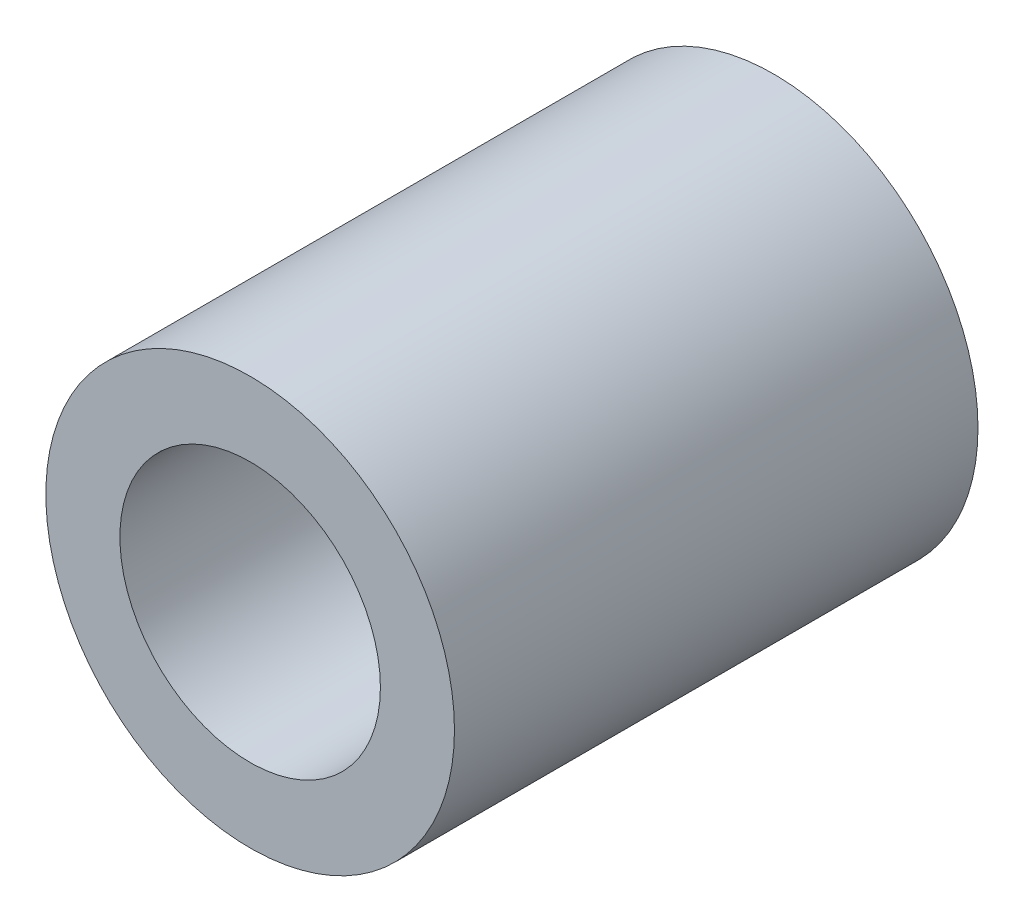
SolidWorks part; units mm, degrees
ref_plane "Front Plane" through (0, 0, 0) normal (0, 0, 1) x (1, 0, 0)
ref_plane "Top Plane" through (0, 0, 0) normal (0, 1, 0) x (1, 0, 0)
ref_plane "Right Plane" through (0, 0, 0) normal (1, 0, 0) x (0, 0, -1)
sketch "Sketch1" plane through (0, 0, 0) normal (0, 0, 1) x (1, 0, 0)
  circle A0 centre (0, 0) radius 8
  dimension "D1" = 16
extrude "Boss-Extrude1" add sketch "Sketch1" along normal blind 20.5
sketch "Sketch2" plane through (0, 0, 20.5) normal (0, 0, 1) x (1, 0, 0)
  circle A0 centre (0, 0) radius 5.1
  circle A1 centre (0, 0) radius 8 construction
  dimension "D1" = 2.9
extrude "Cut-Extrude1" cut sketch "Sketch2" against normal blind 13
sketch "Sketch3" plane through (0, 0, 0) normal (0, 0, -1) x (-1, 0, 0)
  line L0 (-0.9487, 1.35) -> (0.9487, 1.35)
  arc A0 (-0.9487, 1.35) -> (0.9487, 1.35) centre (0, 0) ccw
  dimension "D1" = 3.3
  dimension "D2" = 1.35
extrude "Cut-Extrude2" cut sketch "Sketch3" against normal through all
